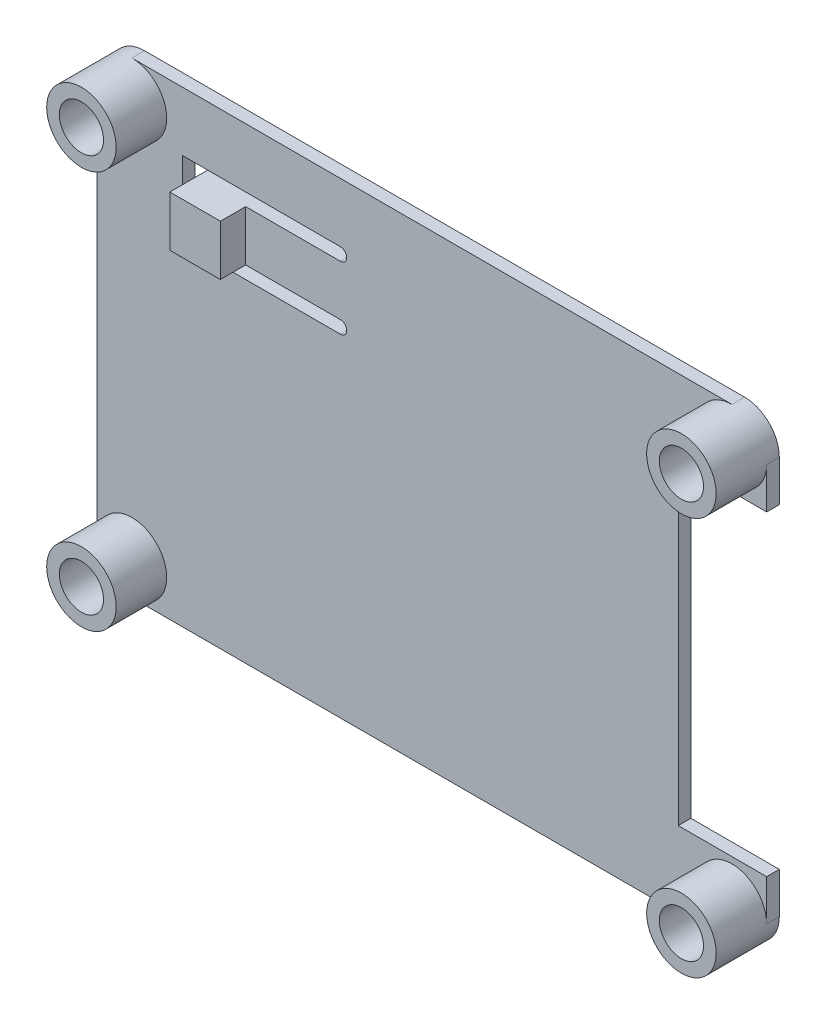
SolidWorks part; units mm, degrees
ref_plane "Plano frontal" through (0, 0, 0) normal (0, 0, 1) x (1, 0, 0)
ref_plane "Plano superior" through (0, 0, 0) normal (0, 1, 0) x (1, 0, 0)
ref_plane "Plano direito" through (0, 0, 0) normal (1, 0, 0) x (0, 0, -1)
sketch "Esboço1" plane through (0, 0, 0) normal (0, 0, 1) x (1, 0, 0)
  line L0 (0, 9.5194) -> (0, 0) construction
  line L1 (0, 0) -> (7.693, 0) construction
  line L2 (-23.75, 18.5) -> (23.75, 18.5)
  line L3 (-26.5, 15.75) -> (-26.5, -15.75)
  line L4 (23.75, -18.5) -> (-23.75, -18.5)
  line L6 (26.5, 15.75) -> (26.5, -15.75)
  circle A0 centre (-23.75, 15.75) radius 2.75
  circle A1 centre (-23.75, 15.75) radius 1.75
  circle A2 centre (23.75, 15.75) radius 1.75
  circle A3 centre (23.75, 15.75) radius 2.75
  circle A4 centre (23.75, -15.75) radius 2.75
  circle A5 centre (23.75, -15.75) radius 1.75
  circle A6 centre (-23.75, -15.75) radius 1.75
  circle A7 centre (-23.75, -15.75) radius 2.75
  point P23 (27, -15.75)
  point P24 (27, 15.75)
  dimension "D1" = 3.5
  dimension "D3" = 1
  dimension "D4" = 5.5
  dimension "D2" = 31.5
  dimension "D5" = 47.5
extrude "Ressalto-extrusão1" add sketch "Esboço1" along normal blind 1 contours A3 L2 A0 L3 A7 L4 A4 L6 | A3 A2 | A4 A5 | A7 A6 | A0 A1 region at (0, 0, 0) region at (-21.8605, 17.6395, 0) region at (25.6395, 17.6395, 0) region at (-23.75, -13.0778, 0) region at (25.6395, -17.6395, 0)
extrude "Ressalto-extrusão2" add sketch "Esboço1<3>" along normal blind 5 contours A0 A1 | A3 A2 | A4 A5 | A7 A6 region at (-21.8605, 17.6395, 0) region at (25.6395, 17.6395, 0) region at (-23.75, -13.0778, 0) region at (25.6395, -17.6395, 0)
sketch "Esboço1<3>" plane through (0, 0, 0) normal (0, 0, 1) x (1, 0, 0) same geometry as "Esboço1"
sketch "Esboço2" plane through (0, 0, 1) normal (0, 0, 1) x (1, 0, 0)
  line L0 (26.5, 15.75) -> (26.5, -15.75) construction
  line L1 (19.5, -12.5) -> (26.5, -12.5)
  line L2 (19.5, -12.5) -> (19.5, 12.5)
  line L3 (19.5, 12.5) -> (26.5, 12.5)
  line L4 (26.5, -12.5) -> (26.5, 12.5)
  line L5 (19.5, -12.5) -> (26.5, 12.5) construction
  line L6 (19.5, 12.5) -> (26.5, -12.5) construction
  arc A0 (23.75, 18.5) -> (26.5, 15.75) centre (23.75, 15.75) ccw construction
  point P0 (23, 0)
  point P10 (0, 0)
  dimension "D2" = 0.5
  dimension "D1" = 7
extrude "Corte-extrusão1" cut sketch "Esboço2" against normal blind 6
sketch "Esboço3" plane through (0, 0, 0) normal (0, 0, -1) x (-1, 0, 0)
  line L0 (7.25, 13.3143) -> (19.25, 13.3143) construction
  line L1 (19.25, 13.3143) -> (19.25, 8.3143) construction
  line L2 (19.25, 8.3143) -> (7.25, 8.3143) construction
  line L3 (7.25, 12.8143) -> (18.75, 12.8143)
  line L4 (18.75, 12.8143) -> (18.75, 8.8143)
  line L5 (18.75, 8.8143) -> (7.25, 8.8143)
  line L6 (7.25, 13.8143) -> (19.75, 13.8143)
  line L7 (19.75, 13.8143) -> (19.75, 7.8143)
  line L8 (19.75, 7.8143) -> (7.25, 7.8143)
  arc A0 (7.25, 12.8143) -> (7.25, 13.8143) centre (7.25, 13.3143) cw
  arc A1 (7.25, 8.8143) -> (7.25, 7.8143) centre (7.25, 8.3143) ccw
  circle A2 centre (23.75, 15.75) radius 1.75 construction
  point P14 (19.25, 10.8143)
  point P15 (5.9777, 12.9943)
  point P16 (0, 0)
  dimension "D4" = 4.9357
  dimension "D3" = 5
  dimension "D5" = 12
  dimension "D6" = 4
  dimension "D1" = 0.5
  dimension "D2" = 0.5
extrude "Corte-extrusão2" cut sketch "Esboço3" against normal blind 6
sketch "Esboço4" plane through (0, 0, 1) normal (0, 0, 1) x (1, 0, 0)
  line L0 (-18.75, 12.8143) -> (-7.25, 12.8143) construction
  line L1 (-18.75, 8.8143) -> (-14.75, 8.8143)
  line L2 (-18.75, 8.8143) -> (-18.75, 12.8143)
  line L3 (-18.75, 12.8143) -> (-14.75, 12.8143)
  line L4 (-14.75, 8.8143) -> (-14.75, 12.8143)
extrude "Ressalto-extrusão3" add sketch "Esboço4" along normal offset from surface (2 mm away) 2 up to face at (-21, -15.75, 5)
